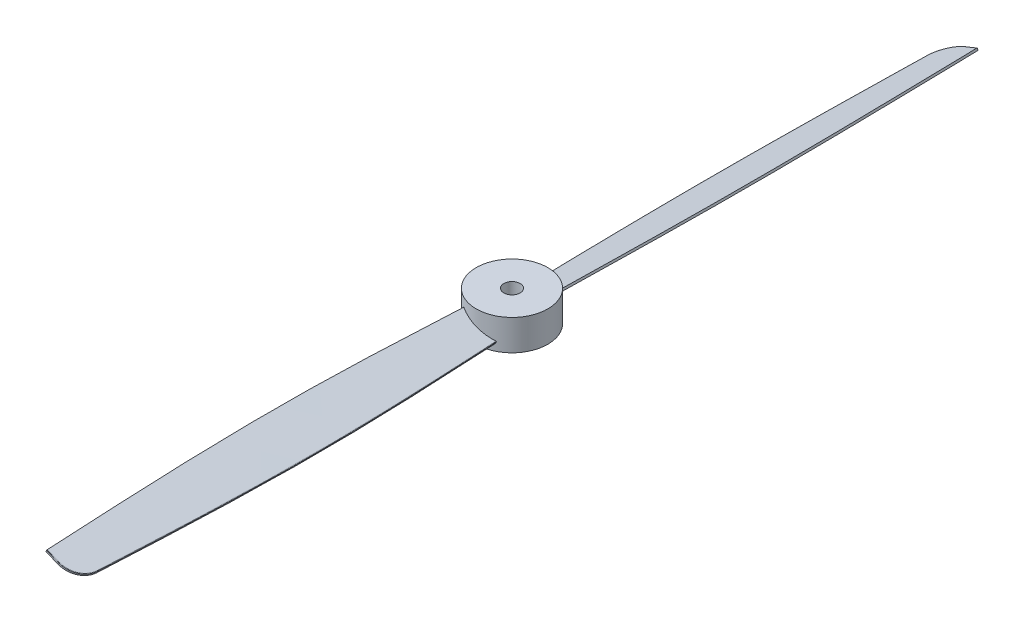
SolidWorks part; units mm, degrees
ref_plane "Front Plane" through (0, 0, 0) normal (0, 0, 1) x (1, 0, 0)
ref_plane "Top Plane" through (0, 0, 0) normal (0, 1, 0) x (1, 0, 0)
ref_plane "Right Plane" through (0, 0, 0) normal (1, 0, 0) x (0, 0, -1)
sketch "Sketch1" plane through (0, 0, 0) normal (0, 1, 0) x (1, 0, 0)
  circle A0 centre (0, 0) radius 17.5
  dimension "D1" = 35
extrude "Boss-Extrude1" add sketch "Sketch1" along normal mid plane 15
sketch "Sketch2" plane through (0, 0, 0) normal (0, 0, 1) x (1, 0, 0)
  line L0 (0, -12.5362) -> (0, 13.1413) construction
  line L1 (-7.4258, 2.9762) -> (7.4258, -2.9762)
  line L2 (-7.4258, 2.9762) -> (-7.7978, 2.048)
  line L3 (7.4258, -2.9762) -> (7.0538, -3.9044)
  line L4 (-7.7978, 2.048) -> (7.0538, -3.9044)
  point P3 (0, 0)
  dimension "D1" = 16
  dimension "D2" = 1
ref_plane "Plane1" through (0, 0, 100) normal (0, 0, 1) x (1, 0, 0)
sketch "Sketch3" plane through (0, 0, 100) normal (0, 0, 1) x (1, 0, 0)
  line L0 (-10.1803, 4.1668) -> (10.1803, -4.1668)
  line L1 (-10.1803, 4.1668) -> (-10.5591, 3.2413)
  line L2 (10.1803, -4.1668) -> (9.8015, -5.0923)
  line L3 (-10.5591, 3.2413) -> (9.8015, -5.0923)
  point P0 (0, 0)
  dimension "D1" = 22
  dimension "D2" = 1
ref_plane "Plane2" through (0, 0, 220) normal (0, 0, 1) x (1, 0, 0)
sketch "Sketch4" plane through (0, 0, 220) normal (0, 0, 1) x (1, 0, 0)
  line L0 (7.4258, -2.9762) -> (7.0538, -3.9044) construction
  line L1 (-7.7978, 2.048) -> (7.0538, -3.9044) construction
  line L2 (-7.4258, 2.9762) -> (7.4258, -2.9762) construction
  line L3 (-7.4258, 2.9762) -> (-7.7978, 2.048) construction
  line L4 (7.4258, -2.9762) -> (7.0538, -3.9044)
  line L5 (-7.7978, 2.048) -> (7.0538, -3.9044)
  line L6 (-7.4258, 2.9762) -> (7.4258, -2.9762)
  line L7 (-7.4258, 2.9762) -> (-7.7978, 2.048)
loft "Loft1" add profiles "Sketch2", "Sketch3", "Sketch4" connector at (7.4258, -2.9762, 0) connector at (10.1803, -4.1668, 100) connector at (7.4258, -2.9762, 220)
fillet "Fillet2" radius 10 1 edges
fillet "Fillet3" radius 0.2 3 edges at (4.3046, -1.7267, 217.8087)
pattern_circular "CirPattern1" count 2 over 360 about axis through (0, 7.5, 0) along (0, 1, 0) of "Fillet3", "Fillet2", "Loft1"
sketch "Sketch5" plane through (0, 7.5, 0) normal (0, 1, 0) x (1, 0, 0)
  circle A0 centre (0, 0) radius 4
  dimension "D1" = 8
extrude "Cut-Extrude1" cut sketch "Sketch5" against normal through all both and the other way through all
